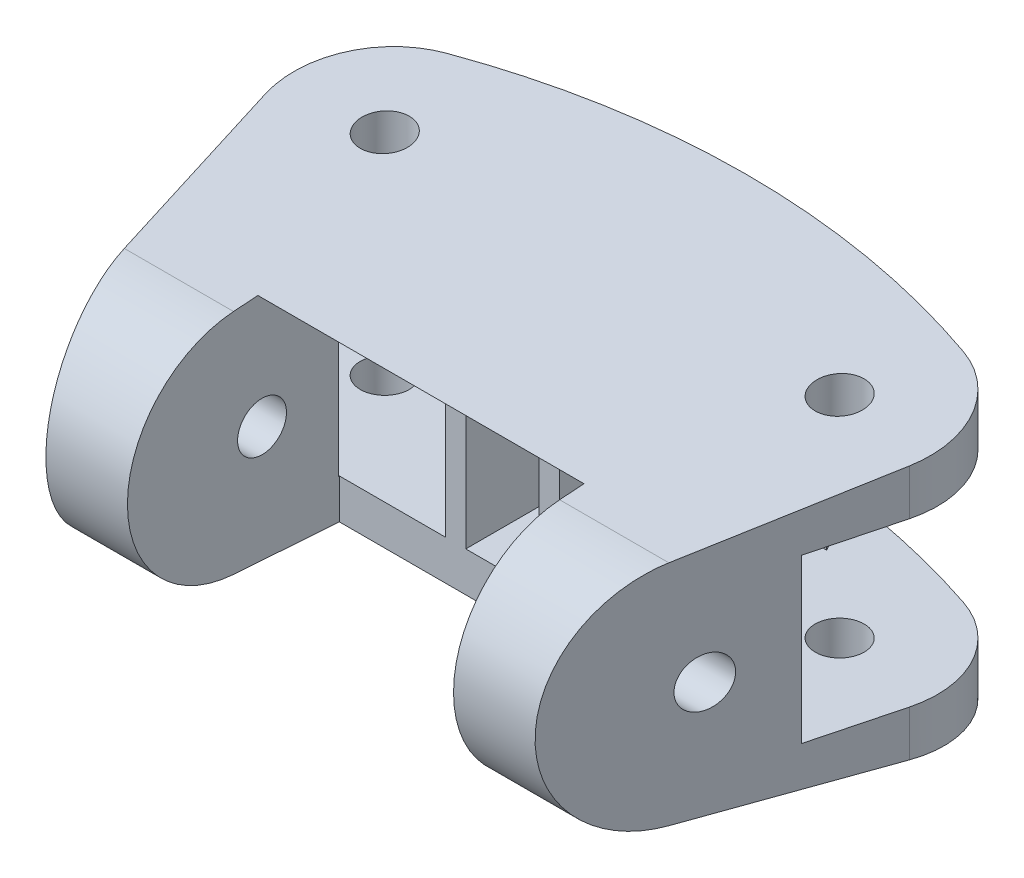
SolidWorks part; units mm, degrees
ref_plane "Front Plane" through (0, 0, 0) normal (0, 0, 1) x (1, 0, 0)
ref_plane "Top Plane" through (0, 0, 0) normal (0, 1, 0) x (1, 0, 0)
ref_plane "Right Plane" through (0, 0, 0) normal (1, 0, 0) x (0, 0, -1)
sketch "Sketch1" plane through (0, 0, 0) normal (0, 1, 0) x (1, 0, 0)
  line L0 (-15, 0) -> (15, 0)
  line L1 (15, 0) -> (19.7554, 18.2144)
  line L2 (0, 0) -> (0, 20.1408) construction
  line L3 (-15, 0) -> (-19.7554, 18.2144)
  arc A0 (19.7554, 18.2144) -> (15.8523, 25.4205) centre (13.95, 19.7301) ccw
  arc A1 (15.8523, 25.4205) -> (-15.8523, 25.4205) centre (0, -22) ccw
  arc A2 (-19.7554, 18.2144) -> (-15.8523, 25.4205) centre (-13.95, 19.7301) cw
  circle A3 centre (-13.95, 19.7301) radius 1.5
  circle A4 centre (13.95, 19.7301) radius 1.5
  point P16 (0, 28)
  dimension "D1" = 30
  dimension "D3" = 3
  dimension "D4" = 28
  dimension "D5" = 6
  dimension "D6" = 50
  dimension "D2" = 27.9
extrude "Extrude1" add sketch "Sketch1" along normal mid plane 17
ref_axis "Axis1" through (-13.95, 8.5, -19.7301) along (0, -1, 0)
sketch "Sketch2" plane through (0, 0, 0) normal (1, 0, 0) x (0, 0, -1)
  line L0 (6.507, 6.9826) -> (29, 8.5706)
  line L1 (-8.4517, 0) -> (42.3813, 0) construction
  line L4 (0, 8.5) -> (0, -8.5) construction
  line L5 (29, 8.5706) -> (29, 9.5706)
  line L6 (29, 9.5706) -> (-1, 9.5706)
  line L7 (-1, 9.5706) -> (-1, -9.5706)
  line L9 (19.7301, 8.5) -> (19.7301, -8.5) construction
  line L10 (28, -8.5) -> (28, 8.5) construction
  line L11 (29, -9.5706) -> (-1, -9.5706)
  line L12 (29, -8.5706) -> (29, -9.5706)
  line L13 (6.507, -6.9826) -> (29, -8.5706)
  arc A0 (6.507, 6.9826) -> (6.507, -6.9826) centre (7, 0) ccw
  circle A1 centre (8.2551, 0) radius 1.5
  point P7 (0, 0)
  point P20 (-1, 0)
  point P24 (0, 0)
  dimension "D3" = 7
  dimension "D5" = 3
  dimension "D1" = 1
  dimension "D2" = 1
  dimension "D4" = 11.475
  dimension "D6" = 1
extrude "Cut-Extrude1" cut sketch "Sketch2" against normal mid plane 50
sketch "Sketch4" plane through (0, 0, 0) normal (1, 0, 0) x (0, 0, -1)
  line L0 (-2, -8.5) -> (13, -8.5)
  line L1 (13, -8.5) -> (13, 5)
  line L2 (13, 5) -> (10.4884, 5)
  line L3 (10.4884, 5) -> (5.1255, 9.5)
  line L4 (5.1255, 9.5) -> (-2, 9.5)
  line L5 (-2, 9.5) -> (-2, -8.5)
  line L6 (18.2144, 7.8091) -> (6.507, 6.9826) construction
  line L7 (13, 5) -> (13, 7.441) construction
  point P3 (8, 7.088)
  dimension "D1" = 1
  dimension "D2" = 2
  dimension "D3" = 40
  dimension "D4" = 20
  dimension "D5" = 5
  dimension "D6" = 15
  dimension "D7" = 5
extrude "Cut-Extrude2" cut sketch "Sketch4" against normal mid plane 20
sketch "Sketch7" plane through (0, 0, 0) normal (0, 1, 0) x (1, 0, 0)
  line L0 (-10, 6.507) -> (-10, 12.9511)
  line L1 (-10, 12.9511) -> (-21.7554, 12.9511)
  line L2 (-21.7554, 12.9511) -> (-21.7554, 29)
  line L4 (-6, 29) -> (-8.8868, 24)
  line L5 (-8.8868, 24) -> (-3.5, 24)
  line L6 (-3.5, 24) -> (-3.5, 8)
  line L7 (-10, 8) -> (10, 8) construction
  line L8 (-3.5, 8) -> (-2.25, 8)
  line L9 (-2.25, 8) -> (-2.25, 24)
  line L10 (-2.25, 24) -> (2.25, 24)
  line L11 (-21.7554, 29) -> (-6, 29)
  line L12 (-10, 6.507) -> (10, 6.507)
  line L13 (0, 0) -> (0, 30.0929) construction
  line L14 (21.7554, 29) -> (6, 29)
  line L15 (2.25, 8) -> (2.25, 24)
  line L16 (3.5, 8) -> (2.25, 8)
  line L17 (3.5, 24) -> (3.5, 8)
  line L18 (8.8868, 24) -> (3.5, 24)
  line L19 (6, 29) -> (8.8868, 24)
  line L21 (21.7554, 12.9511) -> (21.7554, 29)
  line L22 (10, 12.9511) -> (21.7554, 12.9511)
  line L23 (10, 6.507) -> (10, 12.9511)
  line L24 (-15, 0) -> (-10, 0) construction
  arc A1 (15.8523, 25.4205) -> (-15.8523, 25.4205) centre (0, -22) ccw construction
  point P6 (0, 28)
  point P18 (0, 6.507)
  point P24 (0, 24)
  dimension "D1" = 1.25
  dimension "D2" = 12.9511
  dimension "D3" = 4.5
  dimension "D4" = 4
  dimension "D5" = 1
  dimension "D6" = 2
  dimension "D7" = 60
  dimension "D8" = 12
extrude "Cut-Extrude3" cut sketch "Sketch7" against normal mid plane 10
sketch "Sketch8" plane through (0, 0, 0) normal (0, 1, 0) x (1, 0, 0)
  line L0 (-13.95, 19.7301) -> (0, 15.6111) construction
  line L1 (13.95, 19.7301) -> (0, 15.6111) construction
  line L2 (-13.95, 19.7301) -> (13.95, 19.7301) construction
  dimension "D1" = 16.45
